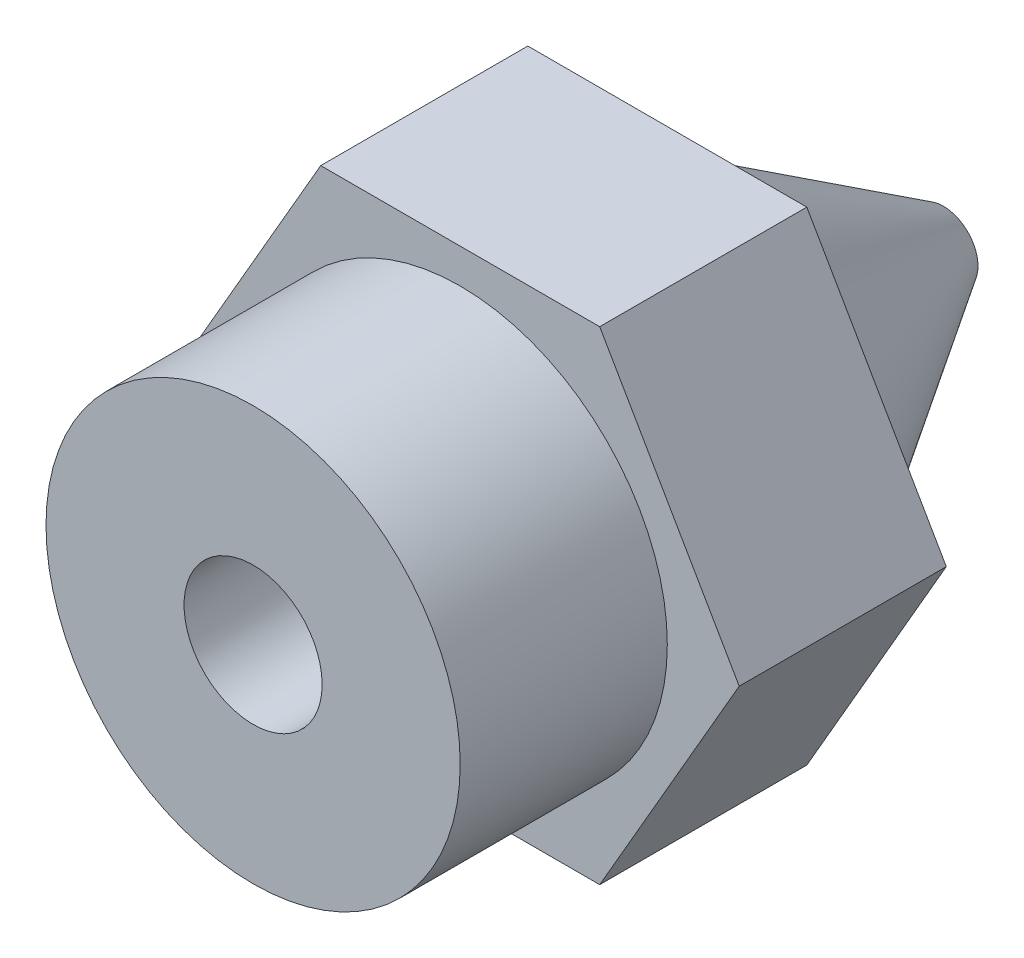
SolidWorks part; units mm, degrees
ref_plane "Plan de face" through (0, 0, 0) normal (0, 0, 1) x (1, 0, 0)
ref_plane "Plan de dessus" through (0, 0, 0) normal (0, 1, 0) x (1, 0, 0)
ref_plane "Plan de droite" through (0, 0, 0) normal (1, 0, 0) x (0, 0, -1)
sketch "Esquisse1" plane through (0, 0, 0) normal (0, 0, 1) x (1, 0, 0)
  line L1 (4.0415, 0) -> (2.0207, 3.5)
  line L2 (2.0207, 3.5) -> (-2.0207, 3.5)
  line L3 (-2.0207, 3.5) -> (-4.0415, 0)
  line L4 (-4.0415, 0) -> (-2.0207, -3.5)
  line L5 (-2.0207, -3.5) -> (2.0207, -3.5)
  line L6 (2.0207, -3.5) -> (4.0415, 0)
  circle A0 centre (0, 0) radius 3.5 construction
  dimension "D1" = 7
extrude "Boss.-Extru.1" add sketch "Esquisse1" along normal blind 10
sketch "Esquisse2" plane through (0, 0, 10) normal (0, 0, 1) x (1, 0, 0)
  line L1 (-7.9912, 5.5023) -> (7.566, 5.5023)
  line L2 (-7.9912, 5.5023) -> (-7.9912, -5.9665)
  line L3 (-7.9912, -5.9665) -> (7.566, -5.9665)
  line L4 (7.566, 5.5023) -> (7.566, -5.9665)
  circle A0 centre (0, 0) radius 3
  dimension "D1" = 6
extrude "Enlèv. mat.-Extru.1" cut sketch "Esquisse2" against normal blind 3
cosmetic thread "Représentation de filetage1" parameters "D2"=4.891
hole_wizard "Diamètre du perçage Ø2.0 (2)1" positions "Esquisse5" profile "Esquisse6" hole size "Ø2.0" standard "ISO"
sketch "Esquisse5" plane through (0, 0, 10) normal (0, 0, 1) x (1, 0, 0)
  point P0 (0, 0)
sketch "Esquisse6" plane through (0, 0, 10) normal (1, 0, 0) x (0, -1, 0)
  line L0 (0, 0) -> (0, 8.6009)
  line L1 (0, 8.6009) -> (1, 8)
  line L2 (1, 8) -> (1, 0)
  line L5 (1, 0) -> (0, 0)
  line L10 (0, 8.6009) -> (-1, 8) construction
  line L11 (0, -6.35) -> (0, 107.95) construction
  dimension "Diamètre du perçage" = 2
  dimension "Profondeur du perçage" = 8
  dimension "Angle de pointe" = 118
hole_wizard "Diamètre du perçage Ø1.5 (1.5)1" positions "Esquisse8" profile "Esquisse7" hole size "Ø1.5" standard "ISO"
sketch "Esquisse8" plane through (0, 0, 10) normal (0, 0, 1) x (1, 0, 0)
  point P0 (0, 0)
sketch "Esquisse7" plane through (0, 0, 10) normal (1, 0, 0) x (0, -1, 0)
  line L0 (0, 0) -> (0, 9.4506)
  line L1 (0, 9.4506) -> (0.75, 9)
  line L2 (0.75, 9) -> (0.75, 0)
  line L5 (0.75, 0) -> (0, 0)
  line L10 (0, 9.4506) -> (-0.75, 9) construction
  line L11 (0, -6.35) -> (0, 107.95) construction
  dimension "Diamètre du perçage" = 1.5
  dimension "Profondeur du perçage" = 9
  dimension "Angle de pointe" = 118
hole_wizard "Diamètre du perçage Ø0.4 (0.4)1" positions "Esquisse10" profile "Esquisse9" hole size "Ø0.4" standard "ISO"
sketch "Esquisse10" plane through (0, 0, 0) normal (0, 0, -1) x (-1, 0, 0)
  point P0 (0, 0)
sketch "Esquisse9" plane through (0, 0, 0) normal (1, 0, 0) x (0, 1, 0)
  line L0 (0, 0) -> (0, 1.1202)
  line L1 (0, 1.1202) -> (0.2, 1)
  line L2 (0.2, 1) -> (0.2, 0)
  line L5 (0.2, 0) -> (0, 0)
  line L10 (0, 1.1202) -> (-0.2, 1) construction
  line L11 (0, -6.35) -> (0, 107.95) construction
  dimension "Diamètre du perçage" = 0.4
  dimension "Profondeur du perçage" = 1
  dimension "Angle de pointe" = 118
sketch "Esquisse3" plane through (0, 0, 0) normal (0, 0, -1) x (-1, 0, 0)
  line L1 (7.8656, -6.0768) -> (-7.4574, -6.0768)
  line L2 (7.8656, -6.0768) -> (7.8656, 5.7844)
  line L3 (7.8656, 5.7844) -> (-7.4574, 5.7844)
  line L4 (-7.4574, -6.0768) -> (-7.4574, 5.7844)
  circle A0 centre (0, 0) radius 3
  dimension "D1" = 6
extrude "Enlèv. mat.-Extru.3" cut sketch "Esquisse3" against normal blind 4
chamfer "Chanfrein2" distance 4 angle 32 1 edges at (-3, 0, 0) first distance on face at (-3, 0, 4)
